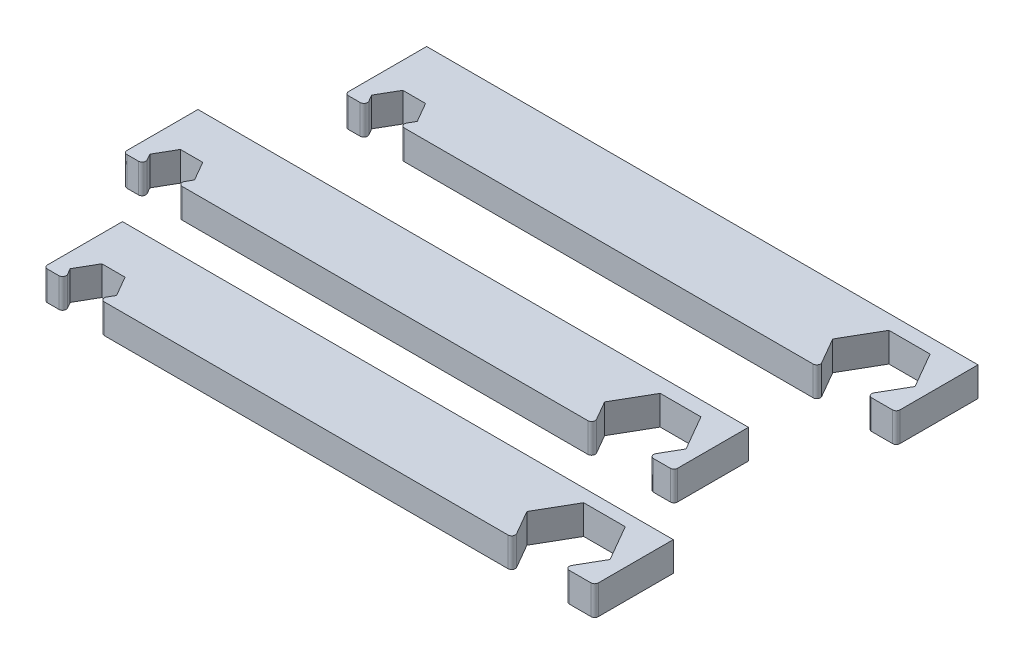
SolidWorks part; units mm, degrees
ref_plane "Front Plane" through (0, 0, 0) normal (0, 0, 1) x (1, 0, 0)
ref_plane "Top Plane" through (0, 0, 0) normal (0, 1, 0) x (1, 0, 0)
ref_plane "Right Plane" through (0, 0, 0) normal (1, 0, 0) x (0, 0, -1)
sketch "Sketch1" plane through (0, 0, 0) normal (0, 1, 0) x (1, 0, 0)
  line L0 (-78.2391, 9.2569) -> (-21.2893, 9.2569)
  line L1 (-22.1054, 28.263) -> (-20.1652, 31.6236)
  line L2 (-20.1652, 31.6236) -> (-22.9509, 36.4486)
  line L3 (-22.9509, 36.4486) -> (-28.5223, 36.4486)
  line L4 (-28.5223, 36.4486) -> (-31.308, 31.6236)
  line L5 (-31.308, 31.6236) -> (-29.3678, 28.263)
  line L6 (-20.6731, 50.3797) -> (-78.3461, 50.3797)
  line L7 (-86.582, 28.263) -> (-85.6523, 29.8733)
  line L8 (-85.6523, 29.8733) -> (-87.1823, 32.5233)
  line L9 (-87.1823, 32.5233) -> (-90.2422, 32.5233)
  line L10 (-90.2422, 32.5233) -> (-91.7722, 29.8733)
  line L11 (-91.7722, 29.8733) -> (-90.8425, 28.263)
  line L12 (-82.6032, 50.3797) -> (-85.5924, 50.3797)
  line L13 (-14.3874, 50.3797) -> (-11.9011, 54.6862)
  line L14 (-11.9011, 54.6862) -> (-14.7157, 59.5612)
  line L15 (-86.6077, 28.263) -> (-29.3678, 28.263)
  line L16 (-14.7157, 59.5612) -> (-20.3448, 59.5612)
  line L17 (-20.3448, 59.5612) -> (-23.1594, 54.6862)
  line L18 (-23.1594, 54.6862) -> (-20.6731, 50.3797)
  line L19 (-10.1631, 61.5643) -> (-85.5924, 61.5643)
  line L20 (-78.316, 50.3797) -> (-77.357, 52.0409)
  line L21 (-77.357, 52.0409) -> (-78.9158, 54.7409)
  line L22 (-78.9158, 54.7409) -> (-82.0335, 54.7409)
  line L23 (-82.0335, 54.7409) -> (-83.5924, 52.0409)
  line L24 (-83.5924, 52.0409) -> (-82.6333, 50.3797)
  line L26 (-85.5924, 61.5643) -> (-85.5924, 50.3797)
  line L27 (-93.7722, 38.4585) -> (-93.7722, 28.263)
  line L28 (-10.1631, 61.5643) -> (-10.1631, 50.3797)
  line L29 (-18.4595, 38.4585) -> (-93.7722, 38.4585)
  line L30 (-10.2959, 20.0097) -> (-85.6523, 20.0097)
  line L33 (-85.6523, 9.2569) -> (-82.7147, 9.2569)
  line L34 (-93.7722, 28.263) -> (-90.8169, 28.263)
  line L35 (-10.1631, 50.3797) -> (-14.3874, 50.3797)
  line L36 (-14.6182, 9.2569) -> (-10.2959, 9.2569)
  line L37 (-22.1054, 28.263) -> (-18.4595, 28.263)
  line L38 (-85.6523, 20.0097) -> (-85.6523, 9.2569)
  line L43 (-18.4595, 38.4585) -> (-18.4595, 28.263)
  line L66 (-10.2959, 20.0097) -> (-10.2959, 9.2569)
  line L70 (-14.6182, 9.2569) -> (-12.2668, 13.3295)
  line L71 (-12.2668, 13.3295) -> (-15.1103, 18.2545)
  line L72 (-15.1103, 18.2545) -> (-20.7972, 18.2545)
  line L73 (-20.7972, 18.2545) -> (-23.6406, 13.3295)
  line L74 (-23.6406, 13.3295) -> (-21.2893, 9.2569)
  line L76 (-77.3015, 10.8552) -> (-78.8892, 13.6052)
  line L77 (-78.8892, 13.6052) -> (-82.0646, 13.6052)
  line L78 (-82.0646, 13.6052) -> (-83.6523, 10.8552)
  line L79 (-83.6523, 10.8552) -> (-82.7295, 9.2569)
  line L81 (-78.2243, 9.2569) -> (-77.3015, 10.8552)
  line L82 (-27.7155, 26.7986) -> (-24.9298, 26.7986) [skipped]
  line L83 (-17.9537, 8.4045) -> (-15.1103, 8.4045) [skipped]
  line L84 (-20.2915, 49.8112) -> (-16.4769, 49.8112) [skipped]
  line L85 (-82.0646, 8.1052) -> (-80.4769, 8.1052) [skipped]
  line L86 (-90.2422, 27.2233) -> (-87.1823, 27.2233) [skipped]
  line L87 (-80.4747, 49.3409) -> (-78.9158, 49.3409) [skipped]
  arc A1 (-86.6077, 28.263) -> (-90.8169, 28.263) centre (-88.7123, 29.8733) ccw construction
  arc A2 (-13.3084, 52.2487) -> (-21.7521, 52.2487) centre (-17.5302, 54.6862) ccw construction
  arc A3 (-78.3461, 50.3797) -> (-82.6032, 50.3797) centre (-80.4747, 52.0409) ccw construction
  arc A4 (-21.5372, 29.2472) -> (-29.8943, 29.175) centre (-25.7366, 31.6236) ccw construction
  arc A6 (-13.6885, 10.867) -> (-22.2189, 10.867) centre (-17.9537, 13.3295) ccw construction
  arc A7 (-78.2391, 9.2569) -> (-82.7147, 9.2569) centre (-80.4769, 10.8552) ccw construction
  point P19 (-48.9769, 54.6885)
  point P36 (-56.4298, 31.6258)
  point P61 (-49.4537, 13.3295)
  dimension "D8" = 9.85
  dimension "D10" = 2
  dimension "D9" = 5.5
  dimension "D6" = 2
  dimension "D7" = 5.4
  dimension "D1" = 63
  dimension "D2" = 5.3
  dimension "D3" = 63
  dimension "D4" = 2
  dimension "D5" = 9.65
extrude "Boss-Extrude1" add sketch "Sketch1" along normal blind 4 contours L81 L0 L74 L73 L72 L71 L70 L36 L66 L38 L33 L79 L78 L77 L76 | L43 L27 L34 L11 L10 L9 L8 L7 L15 L5 L4 L3 L2 L1 L37 | L35 L28 L26 L12 L24 L23 L22 L21 L20 L6 L18 L17 L16 L14 L13 region at (-50.3081, 0, -14.8472) region at (-58.328, 0, -33.5814) region at (-50.1625, 0, -56.1896)
chamfer "Chamfer1" distance 25 angle 11.25 rebuild error yes
chamfer "Chamfer2" distance 25 angle 11.25 rebuild error yes
chamfer "Chamfer3" distance 25 angle 11.25 rebuild error yes
fillet "Fillet1" radius 5 rebuild error yes
fillet "Fillet2" radius 0.5 6 edges at (-85.5924, 2, -50.3797) (-78.316, 2, -50.3797) (-82.6333, 2, -50.3797) (-10.1631, 2, -50.3797) (-20.6731, 2, -50.3797) (-14.3874, 2, -50.3797)
fillet "Fillet3" radius 5 rebuild error yes
fillet "Fillet4" radius 0.5 6 edges at (-18.4595, 2, -28.263) (-22.1054, 2, -28.263) (-29.3678, 2, -28.263) (-86.582, 2, -28.263) (-90.8425, 2, -28.263) (-93.7722, 2, -28.263)
fillet "Fillet5" radius 0.5 6 edges at (-10.2959, 2, -9.2569) (-14.6182, 2, -9.2569) (-21.2893, 2, -9.2569) (-78.2243, 2, -9.2569) (-82.7295, 2, -9.2569) (-85.6523, 2, -9.2569)
fillet "Fillet6" radius 5 rebuild error yes
